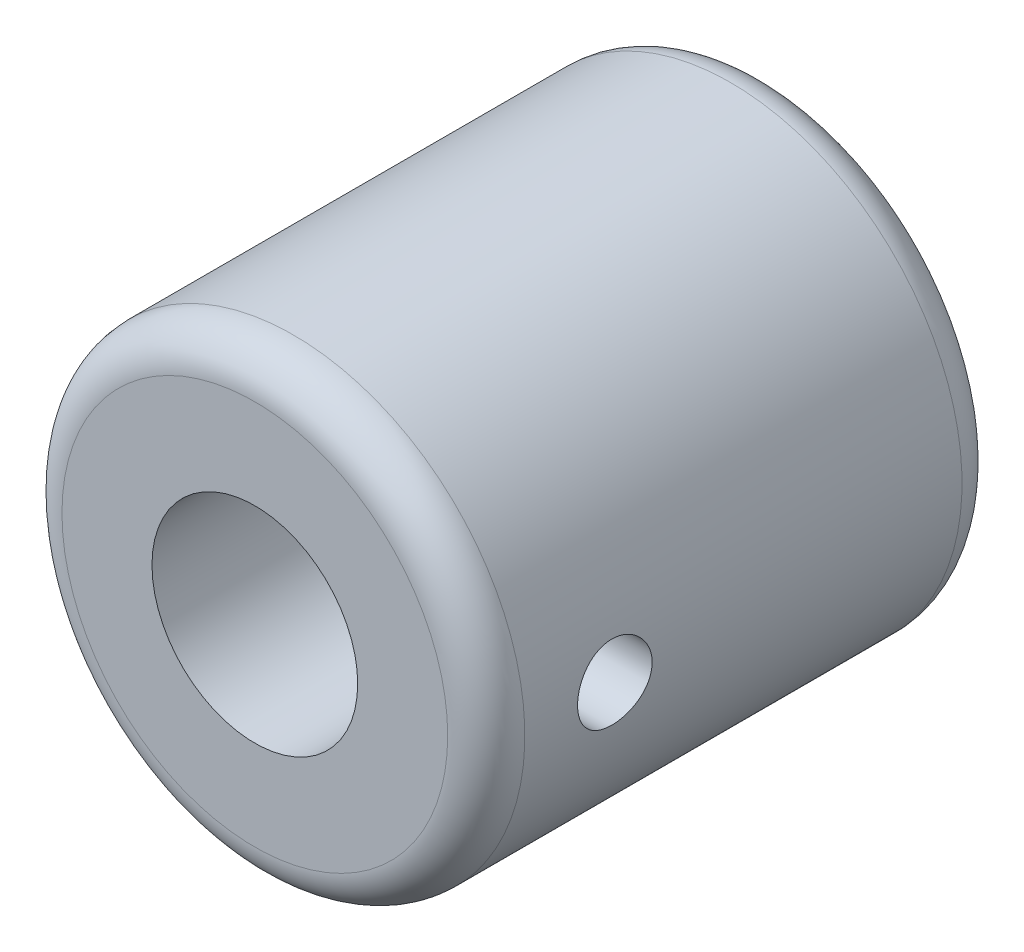
SolidWorks part; units mm, degrees
material "ABS"
ref_plane "Front Plane" through (0, 0, 0) normal (0, 0, 1) x (1, 0, 0)
ref_plane "Top Plane" through (0, 0, 0) normal (0, 1, 0) x (1, 0, 0)
ref_plane "Right Plane" through (0, 0, 0) normal (1, 0, 0) x (0, 0, -1)
ref_plane "Plane1" through (0, 0, 0) normal (0, -1, 0) x (1, 0, 0)
sketch "Sketch1" plane through (0, 0, 0) normal (0, -1, 0) x (1, 0, 0)
  line L0 (7.5, 20) -> (0, 20)
  line L1 (0, 20) -> (0, 0)
  line L2 (0, 0) -> (7.5, 0)
  line L3 (9, 1.5) -> (9, 18.5)
  line L4 (0, 20) -> (0, 0) construction
  arc A0 (7.5, 0) -> (9, 1.5) centre (7.5, 1.5) ccw
  arc A1 (9, 18.5) -> (7.5, 20) centre (7.5, 18.5) ccw
  dimension "D1" = 9
revolve "Revolve1" add sketch "Sketch1" angle 360 about L4 reverse direction yes
hole_wizard "Ø8.0 (8) Diameter Hole1" positions "Sketch3" profile "Sketch2" hole size "Ø8.0" standard "ANSI Metric"
sketch "Sketch3" plane through (0, 0, 20) normal (0, 0, 1) x (1, 0, 0)
  point P0 (0, 0)
sketch "Sketch2" plane through (0, 0, 20) normal (1, 0, 0) x (0, -1, 0)
  line L0 (0, 0) -> (0, 10)
  line L1 (0, 10) -> (4, 10)
  line L2 (4, 10) -> (4, 0)
  line L5 (4, 0) -> (0, 0)
  line L10 (0, 10) -> (-4, 10) construction
  line L11 (0, -6.35) -> (0, 107.95) construction
  dimension "Hole Dia." = 8
  dimension "Hole Depth" = 10
  dimension "Drill Angle" = 180
ref_plane "Plane2" through (3.7279, 0, 0) normal (-1, 0, 0) x (0, 0, 1)
hole_wizard "Ø2.9 (2.9) Diameter Hole1" positions "Sketch5" profile "Sketch4" hole size "Ø2.9" standard "ANSI Metric"
sketch "Sketch5" plane through (3.7279, 0, 0) normal (-1, 0, 0) x (0, 0, 1)
  point P0 (15, 0)
sketch "Sketch4" plane through (3.7279, 0, 15) normal (0, 1, 0) x (0, 0, 1)
  line L0 (0, 0) -> (0, 18)
  line L1 (0, 18) -> (1.45, 18)
  line L2 (1.45, 18) -> (1.45, 0)
  line L5 (1.45, 0) -> (0, 0)
  line L10 (0, 18) -> (-1.45, 18) construction
  line L11 (0, -6.35) -> (0, 107.95) construction
  dimension "Hole Dia." = 2.9
  dimension "Hole Depth" = 18
  dimension "Drill Angle" = 180
